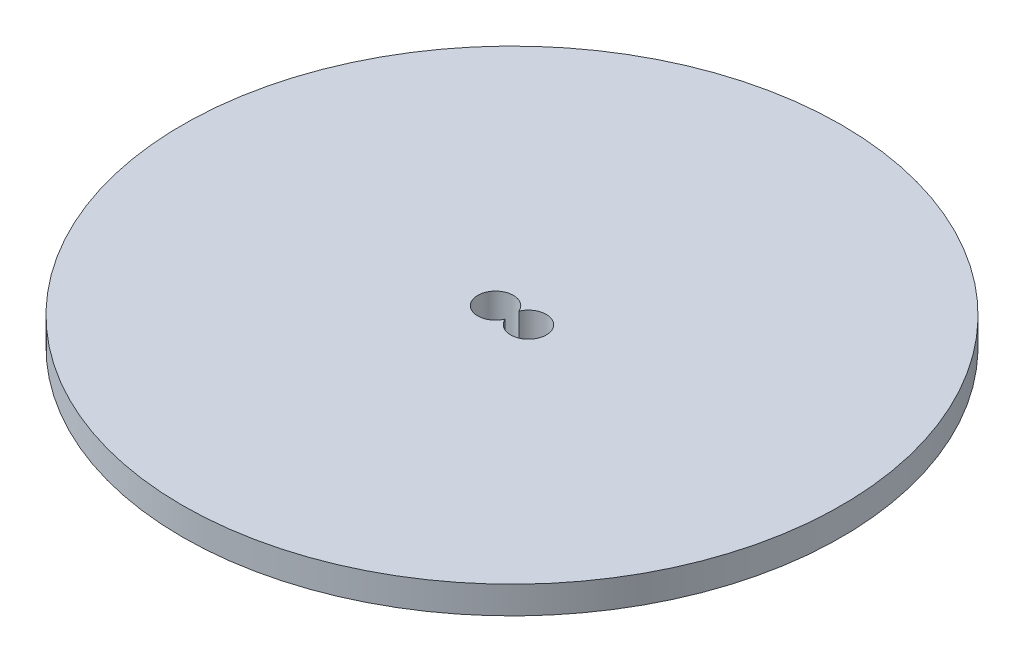
SolidWorks part; units mm, degrees
ref_plane "Front Plane" through (0, 0, 0) normal (0, 0, 1) x (1, 0, 0)
ref_plane "Top Plane" through (0, 0, 0) normal (0, 1, 0) x (1, 0, 0)
ref_plane "Right Plane" through (0, 0, 0) normal (1, 0, 0) x (0, 0, -1)
sketch "Sketch1" plane through (0, 0, 0) normal (0, 1, 0) x (1, 0, 0)
  circle A0 centre (0, 0) radius 60
  dimension "D1" = 120
extrude "Boss-Extrude1" add sketch "Sketch1" along normal blind 5
sketch "Sketch3" plane through (0, 0, 0) normal (0, -1, 0) x (1, 0, 0)
  line L1 (-7, -3.5) -> (7, -3.5)
  line L2 (-7, -3.5) -> (-7, 3.5)
  line L3 (-7, 3.5) -> (7, 3.5)
  line L4 (7, -3.5) -> (7, 3.5)
  line L5 (-7, -3.5) -> (7, 3.5) construction
  line L6 (-7, 3.5) -> (7, -3.5) construction
  point P0 (0, 0)
  dimension "D1" = 14
  dimension "D2" = 7
extrude "Boss-Extrude2" add sketch "Sketch3" along normal blind 5
sketch "Sketch4" plane through (0, 5, 0) normal (0, 1, 0) x (1, 0, 0)
  circle A0 centre (-3, 0) radius 3.25
  circle A1 centre (3, 0) radius 3.25
  dimension "D1" = 6.5
  dimension "D2" = 6.5
  dimension "D3" = 6
  dimension "D4" = 3
extrude "Cut-Extrude1" cut sketch "Sketch4" against normal blind 9 contours A1 A0 | A0 A1 | A0 A1 region at (0, 5, 0) region at (3.0779, 5, 0) region at (-3.0779, 5, 0)
sketch "Sketch7" plane through (0, -4, 0) normal (0, 1, 0) x (1, 0, 0)
  circle A0 centre (-3, 0) radius 1.75
  circle A1 centre (3, 0) radius 1.75
  point P0 (-3, 0)
  point P1 (3, 0)
  dimension "D1" = 3.5
  dimension "D2" = 3.5
extrude "Cut-Extrude2" cut sketch "Sketch7" against normal blind 5
fillet "Fillet1" radius 10 4 edges at (0, 0, 3.5) (7, 0, 0) (-7, 0, 0) (0, 0, -3.5)
